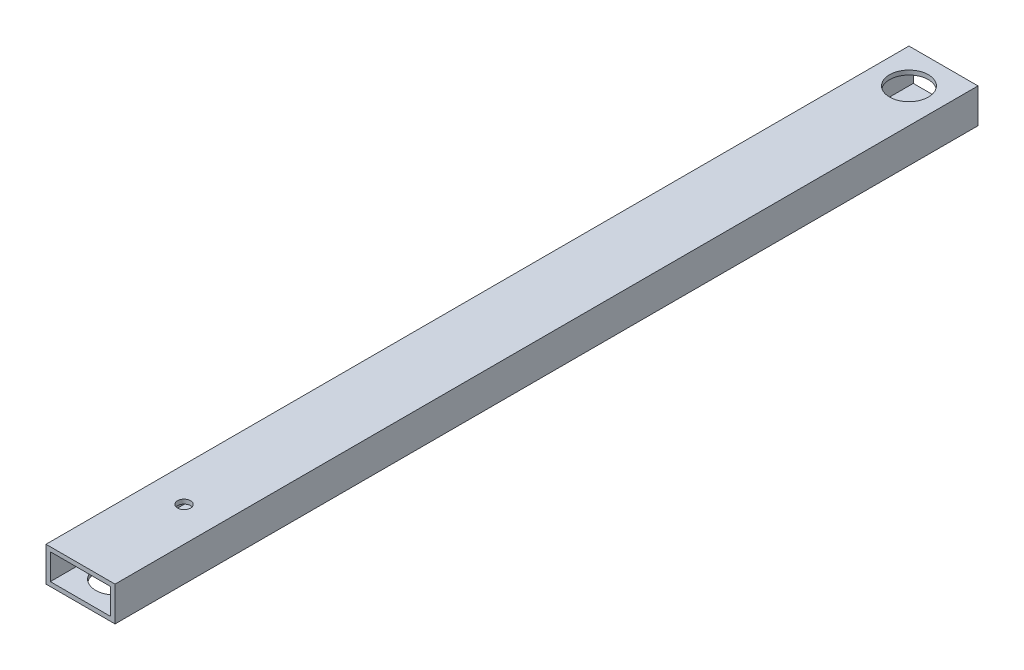
SolidWorks part; units mm, degrees
ref_plane "Front Plane" through (0, 0, 0) normal (0, 0, 1) x (1, 0, 0)
ref_plane "Top Plane" through (0, 0, 0) normal (0, 1, 0) x (1, 0, 0)
ref_plane "Right Plane" through (0, 0, 0) normal (1, 0, 0) x (0, 0, -1)
sketch "Sketch1" plane through (0, 0, 0) normal (0, 0, 1) x (1, 0, 0)
  line L1 (0, 0) -> (50.8, 0)
  line L2 (0, 0) -> (0, 25.4)
  line L3 (0, 25.4) -> (50.8, 25.4)
  line L4 (50.8, 0) -> (50.8, 25.4)
extrude "Boss-Extrude1" add sketch "Sketch1" along normal blind 635
sketch "Sketch2" plane through (0, 0, 0) normal (0, 0, -1) x (-1, 0, 0)
  line L1 (-3.175, 3.175) -> (-47.625, 3.175)
  line L2 (-3.175, 3.175) -> (-3.175, 22.225)
  line L3 (-3.175, 22.225) -> (-47.625, 22.225)
  line L4 (-47.625, 3.175) -> (-47.625, 22.225)
extrude "Cut-Extrude1" cut sketch "Sketch2" against normal blind 635
sketch "Sketch6" plane through (0, 25.4, 0) normal (0, 1, 0) x (1, 0, 0)
  line L0 (25.4, 0) -> (25.4, -25.4) construction
  line L1 (50.8, 0) -> (0, 0) construction
  circle A0 centre (25.4, -25.4) radius 14.2875
extrude "Cut-Extrude5" cut sketch "Sketch6" against normal blind 25.4
sketch "Sketch7" plane through (0, 0, 0) normal (0, -1, 0) x (1, 0, 0)
  line L0 (25.4, 635) -> (25.4, 609.6) construction
  line L1 (0, 635) -> (50.8, 635) construction
  circle A0 centre (25.4, 609.6) radius 14.2875
extrude "Cut-Extrude6" cut sketch "Sketch7" against normal blind 3.175
sketch "Sketch8" plane through (0, 25.4, 0) normal (0, 1, 0) x (1, 0, 0)
  line L0 (25.4, -635) -> (25.4, -558.8) construction
  line L1 (50.8, -635) -> (0, -635) construction
  circle A0 centre (25.4, -558.8) radius 4.7625
extrude "Cut-Extrude7" cut sketch "Sketch8" against normal blind 25.4
